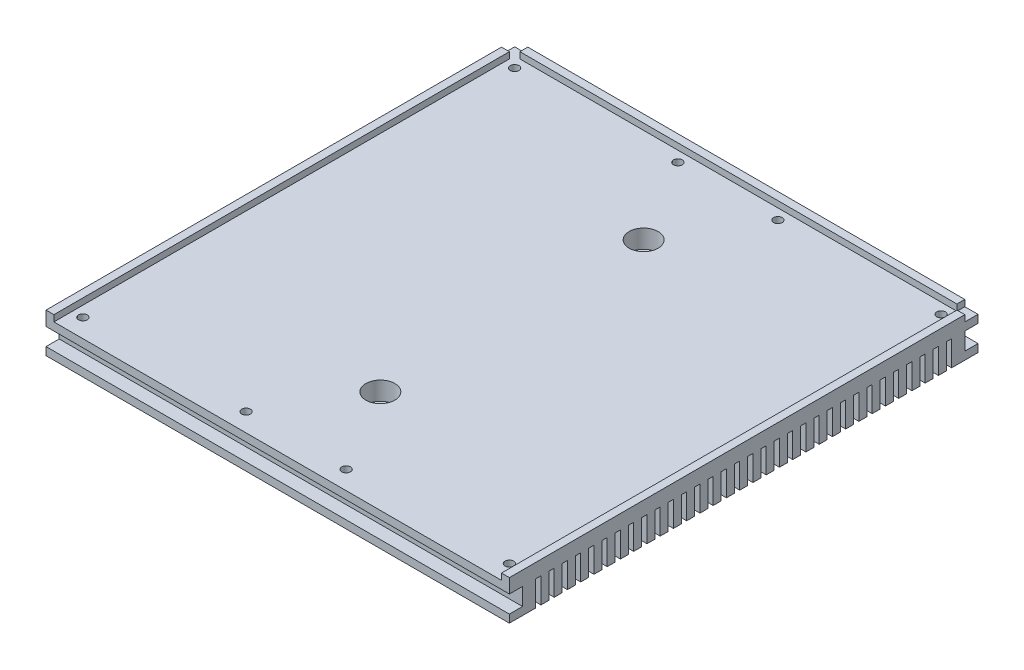
SolidWorks part; units mm, degrees
material "6061 合金"
ref_plane "前视基准面" through (0, 0, 0) normal (0, 0, 1) x (1, 0, 0)
ref_plane "上视基准面" through (0, 0, 0) normal (0, 1, 0) x (1, 0, 0)
ref_plane "右视基准面" through (0, 0, 0) normal (1, 0, 0) x (0, 0, -1)
sketch "草图1" plane through (0, 12.6, 0) normal (0, 1, 0) x (1, 0, 0)
  line L0 (-100.7481, -361.7245) -> (-100.7481, -517.7245) construction
  line L1 (72.2519, -528.7245) -> (-103.7481, -528.7245)
  line L2 (72.2519, -528.7245) -> (72.2519, -350.7245)
  line L3 (72.2519, -350.7245) -> (-103.7481, -350.7245)
  line L4 (-103.7481, -528.7245) -> (-103.7481, -350.7245)
  line L5 (7.2519, -525.7245) -> (61.2519, -525.7245) construction
  line L6 (69.2519, -517.7245) -> (69.2519, -361.7245) construction
  line L9 (61.2519, -353.7245) -> (7.2519, -353.7245) construction
  dimension "D1" = 3
  dimension "D2" = 3
  dimension "D3" = 3
  dimension "D4" = 3
extrude "凸台-拉伸1" add sketch "草图1" against normal up to surface (12.6 mm away)
sketch "草图3" plane through (0, 12.6, 0) normal (0, 1, 0) x (1, 0, 0)
  line L0 (-15.7481, -539.7245) -> (-15.7481, -489.7245) construction
  line L1 (-15.7481, -489.7245) -> (-15.7481, -389.7245) construction
  dimension "D1" = 50
  dimension "D2" = 100
hole_wizard "打孔尺寸(%根据)内六角圆柱头螺钉的类型1" positions "3D草图1" profile "草图4" counterbore size "M6" standard "GB" end condition through all
sketch3d "3D草图1"
  point P0 (-15.7481, 12.6, 389.7245)
  point P3 (-15.7481, 12.6, 489.7245)
sketch "草图4" plane through (-15.7481, 12.6, 389.7245) normal (1, 0, 0) x (0, 0, 1)
  line L0 (0, 0) -> (0, 12.6)
  line L1 (0, 12.6) -> (3.3, 12.6)
  line L3 (3.3, 12.6) -> (3.3, 7)
  line L4 (3.3, 7) -> (5.5, 7)
  line L5 (5.5, 7) -> (5.5, 0)
  line L7 (5.5, 0) -> (0, 0)
  line L11 (0, -6.35) -> (0, 107.95) construction
  dimension "通孔孔直径" = 6.6
  dimension "通孔孔深度" = 12.6
  dimension "柱形沉头孔直径" = 11
  dimension "柱形沉头孔深度" = 7
sketch "草图5" plane through (0, 0, 528.7245) normal (0, 0, 1) x (1, 0, 0)
  line L0 (72.2519, 0) -> (-103.7481, 0) construction
  line L1 (-98.7481, 0) -> (-96.7481, 0)
  line L2 (-98.7481, 0) -> (-98.7481, 7.6)
  line L3 (-98.7481, 7.6) -> (-96.7481, 7.6)
  line L4 (-96.7481, 0) -> (-96.7481, 7.6)
  line L5 (-103.7481, 0) -> (-103.7481, 12.6) construction
  line L6 (-103.7481, 12.6) -> (72.2519, 12.6) construction
  dimension "D1" = 5
  dimension "D2" = 5
  dimension "D3" = 2
extrude "切除-拉伸2" [suppressed] cut sketch "草图5" against normal through all
pattern_linear "阵列(线性)1" [suppressed] count 30 spacing 5.6552 of bodies 104
sketch "草图6" [suppressed] plane through (0, 0, 0) normal (0, -1, 0) x (1, 0, 0)
  line L0 (-8.2654, 528.7245) -> (-23.2309, 528.7245) construction
  line L1 (-19.5757, 528.7245) -> (-17.5757, 528.7245)
  line L2 (-19.5757, 528.7245) -> (-19.5757, 498.7245)
  line L3 (-19.5757, 498.7245) -> (-17.5757, 498.7245)
  line L4 (-17.5757, 528.7245) -> (-17.5757, 498.7245)
  line L5 (-25.2309, 528.7245) -> (-23.2309, 528.7245) construction
  line L6 (-25.2309, 528.7245) -> (-28.8861, 528.7245) construction
  line L7 (-19.5757, 528.7245) -> (-23.2309, 528.7245) construction
  line L8 (-17.5757, 528.7245) -> (-13.9205, 528.7245) construction
  line L9 (-13.9205, 528.7245) -> (-11.9205, 528.7245)
  line L10 (-13.9205, 528.7245) -> (-13.9205, 498.7245)
  line L11 (-13.9205, 498.7245) -> (-11.9205, 498.7245)
  line L12 (-11.9205, 528.7245) -> (-11.9205, 498.7245)
  line L13 (-23.2309, 350.7245) -> (-8.2654, 350.7245) construction
  line L14 (-19.5757, 350.7245) -> (-17.5757, 350.7245)
  line L15 (-19.5757, 350.7245) -> (-19.5757, 380.7245)
  line L16 (-19.5757, 380.7245) -> (-17.5757, 380.7245)
  line L17 (-17.5757, 350.7245) -> (-17.5757, 380.7245)
  line L19 (-13.9205, 350.7245) -> (-11.9205, 350.7245)
  line L20 (-13.9205, 350.7245) -> (-13.9205, 380.7245)
  line L21 (-13.9205, 380.7245) -> (-11.9205, 380.7245)
  line L22 (-11.9205, 350.7245) -> (-11.9205, 380.7245)
  dimension "D1" = 30
  dimension "D2" = 30
extrude "切除-拉伸3" [suppressed] cut sketch "草图6" against normal up to surface (7.6 mm away)
sketch "草图7" plane through (0, 12.6, 0) normal (0, 1, 0) x (1, 0, 0)
  line L0 (69.2519, -528.7245) -> (69.2519, -353.7245)
  line L1 (69.2519, -353.7245) -> (-100.7481, -353.7245)
  line L2 (-100.7481, -353.7245) -> (-100.7481, -528.7245)
  line L3 (69.2519, -528.7245) -> (72.2519, -528.7245)
  line L4 (72.2519, -528.7245) -> (72.2519, -350.7245)
  line L5 (72.2519, -350.7245) -> (-103.7481, -350.7245)
  line L6 (-103.7481, -350.7245) -> (-103.7481, -528.7245)
  line L7 (-103.7481, -528.7245) -> (72.2519, -528.7245)
  line L8 (72.2519, -528.7245) -> (72.2519, -350.7245)
  line L9 (72.2519, -350.7245) -> (-103.7481, -350.7245)
  line L10 (-103.7481, -350.7245) -> (-103.7481, -528.7245)
  line L11 (-103.7481, -528.7245) -> (-100.7481, -528.7245)
  dimension "D1" = 0
  dimension "D2" = 3
extrude "凸台-拉伸3" add sketch "草图7" along normal offset from surface (2.4 mm away) 15 up to face at (-15.7481, 0, 393.0245)
sketch "草图8" plane through (0, 15, 0) normal (0, 1, 0) x (1, 0, 0)
  line L1 (-103.7481, -350.7245) -> (-98.7481, -350.7245)
  line L2 (-103.7481, -350.7245) -> (-103.7481, -355.7245)
  line L3 (-103.7481, -355.7245) -> (-98.7481, -355.7245)
  line L4 (-98.7481, -350.7245) -> (-98.7481, -355.7245)
  line L5 (72.2519, -350.7245) -> (67.2519, -350.7245)
  line L6 (72.2519, -350.7245) -> (72.2519, -355.7245)
  line L7 (72.2519, -355.7245) -> (67.2519, -355.7245)
  line L8 (67.2519, -350.7245) -> (67.2519, -355.7245)
  dimension "D1" = 5
  dimension "D2" = 5
  dimension "D3" = 5
  dimension "D4" = 5
extrude "切除-拉伸4" cut sketch "草图8" against normal up to surface (2.4 mm away) up to face at (-15.7481, 12.6, 441.2245)
sketch "草图9" plane through (0, 12.6, 0) normal (0, 1, 0) x (1, 0, 0)
  line L1 (-96.7481, -357.7245) -> (-34.7481, -357.7245)
  line L2 (-96.7481, -357.7245) -> (-96.7481, -521.7245)
  line L3 (-96.7481, -521.7245) -> (-34.7481, -521.7245)
  line L4 (-34.7481, -357.7245) -> (-34.7481, -521.7245)
  line L5 (3.2519, -521.7245) -> (65.2519, -521.7245)
  line L6 (3.2519, -521.7245) -> (3.2519, -357.7245)
  line L7 (3.2519, -357.7245) -> (65.2519, -357.7245)
  line L8 (65.2519, -521.7245) -> (65.2519, -357.7245)
hole_wizard "M4 螺纹孔1" positions "3D草图2" profile "草图10" tap size "M4" standard "GB"
sketch3d "3D草图2"
  point P0 (-96.7481, 12.6, 357.7245)
  point P3 (-34.7481, 12.6, 357.7245)
  point P6 (-34.7481, 12.6, 521.7245)
  point P9 (-96.7481, 12.6, 521.7245)
  point P12 (3.2519, 12.6, 521.7245)
  point P15 (65.2519, 12.6, 521.7245)
  point P18 (65.2519, 12.6, 357.7245)
  point P21 (3.2519, 12.6, 357.7245)
sketch "草图10" plane through (-96.7481, 12.6, 357.7245) normal (1, 0, 0) x (0, 0, 1)
  line L0 (0, 0) -> (0, 5.9914)
  line L1 (0, 5.9914) -> (1.65, 5)
  line L2 (1.65, 5) -> (1.65, 0)
  line L5 (1.65, 0) -> (0, 0)
  line L10 (0, 5.9914) -> (-1.65, 5) construction
  line L11 (0, -6.35) -> (0, 107.95) construction
  dimension "螺纹孔钻头直径" = 3.3
  dimension "螺纹孔钻头深度" = 5
  dimension "导头角度" = 118
cosmetic thread "孔螺蚊线1" parameters "D1"=5, "D2"=4
cosmetic thread "孔螺蚊线2" parameters "D1"=5, "D2"=4
cosmetic thread "孔螺蚊线3" parameters "D1"=5, "D2"=4
cosmetic thread "孔螺蚊线4" parameters "D1"=5, "D2"=4
cosmetic thread "孔螺蚊线5" parameters "D1"=5, "D2"=4
cosmetic thread "孔螺蚊线6" parameters "D1"=5, "D2"=4
cosmetic thread "孔螺蚊线7" parameters "D1"=5, "D2"=4
cosmetic thread "孔螺蚊线8" parameters "D1"=5, "D2"=4
sketch "草图11" plane through (0, 0, 0) normal (0, -1, 0) x (1, 0, 0)
  line L0 (-15.7481, 489.7245) -> (-15.7481, 479.7245) construction
  line L1 (-15.7481, 489.7245) -> (-15.7481, 389.7245) construction
  line L2 (-15.7481, 389.7245) -> (-15.7481, 399.7245) construction
  dimension "D1" = 10
  dimension "D2" = 10
hole_wizard "大小mm 暗销孔1" positions "3D草图3" profile "草图12" hole size "Ø4.0" standard "GB"
sketch3d "3D草图3"
  point P0 (-15.7481, 0, 479.7245)
sketch "草图12" plane through (-15.7481, 0, 479.7245) normal (1, 0, 0) x (0, 0, -1)
  line L0 (0, 0) -> (0, 6.2017)
  line L1 (0, 6.2017) -> (2, 5)
  line L2 (2, 5) -> (2, 0)
  line L5 (2, 0) -> (0, 0)
  line L10 (0, 6.2017) -> (-2, 5) construction
  line L11 (0, -6.35) -> (0, 107.95) construction
  dimension "孔直径" = 4
  dimension "孔深度" = 5
  dimension "导头角度" = 118
sketch "草图13" plane through (0, 0, 0) normal (0, -1, 0) x (1, 0, 0)
  line L0 (-15.7481, 398.7245) -> (-15.7481, 400.7245) construction
  line L1 (-15.7481, 489.7245) -> (-15.7481, 389.7245) construction
  line L2 (-17.7481, 398.7245) -> (-17.7481, 400.7245)
  line L3 (-13.7481, 398.7245) -> (-13.7481, 400.7245)
  arc A0 (-17.7481, 398.7245) -> (-13.7481, 398.7245) centre (-15.7481, 398.7245) ccw
  arc A1 (-13.7481, 400.7245) -> (-17.7481, 400.7245) centre (-15.7481, 400.7245) ccw
  point P5 (-15.7481, 399.7245)
  dimension "D1" = 2
  dimension "D2" = 2
extrude "切除-拉伸5" cut sketch "草图13" against normal blind 5
sketch "草图14" plane through (-103.7481, 0, 0) normal (-1, 0, 0) x (0, 0, 1)
  line L0 (355.7245, 12.6) -> (350.7245, 12.6) construction
  line L1 (528.7245, 3) -> (523.7245, 3)
  line L2 (528.7245, 3) -> (528.7245, 9.6)
  line L3 (528.7245, 9.6) -> (523.7245, 9.6)
  line L4 (523.7245, 3) -> (523.7245, 9.6)
  line L5 (350.7245, 3) -> (355.7245, 3)
  line L6 (350.7245, 3) -> (350.7245, 9.6)
  line L7 (350.7245, 9.6) -> (355.7245, 9.6)
  line L8 (355.7245, 3) -> (355.7245, 9.6)
  line L9 (528.7245, 0) -> (350.7245, 0) construction
  line L10 (528.7245, 0) -> (528.7245, 15) construction
  dimension "D1" = 3
  dimension "D2" = 3
  dimension "D3" = 5
extrude "切除-拉伸6" cut sketch "草图14" against normal through all
sketch "草图15" plane through (-103.7481, 0, 0) normal (-1, 0, 0) x (0, 0, 1)
  line L0 (528.7245, 0) -> (350.7245, 0) construction
  line L1 (518.7245, 0) -> (516.7245, 0)
  line L2 (518.7245, 0) -> (518.7245, 9.6)
  line L3 (518.7245, 9.6) -> (516.7245, 9.6)
  line L4 (516.7245, 0) -> (516.7245, 9.6)
  line L5 (523.7245, 9.6) -> (523.7245, 3) construction
  line L6 (528.7245, 9.6) -> (523.7245, 9.6) construction
  dimension "D1" = 2
  dimension "D2" = 5
extrude "切除-拉伸7" cut sketch "草图15" against normal through all
pattern_linear "阵列(线性)3" count 32 spacing 5.0323 along (0, 0, -1) skipping (5, 0), (6, 0), (7, 0), (8, 0), (23, 0), (24, 0), (25, 0), (26, 0) of "切除-拉伸7"
sketch "草图16" plane through (0, 0, 0) normal (0, -1, 0) x (1, 0, 0)
  line L0 (-103.7481, 496.5955) -> (-103.7481, 473.4342) construction
  line L1 (-103.7481, 493.5632) -> (-23.2481, 493.5632)
  line L2 (-103.7481, 493.5632) -> (-103.7481, 491.5632)
  line L3 (-103.7481, 491.5632) -> (-23.2481, 491.5632)
  line L4 (-23.2481, 493.5632) -> (-23.2481, 491.5632)
  line L5 (72.2519, 473.4342) -> (72.2519, 496.5955) construction
  line L6 (72.2519, 493.5632) -> (-8.2481, 493.5632)
  line L7 (72.2519, 493.5632) -> (72.2519, 491.5632)
  line L8 (72.2519, 491.5632) -> (-8.2481, 491.5632)
  line L9 (-8.2481, 493.5632) -> (-8.2481, 491.5632)
  line L10 (-15.7481, 539.7245) -> (-15.7481, 489.7245) construction
  line L11 (-15.7481, 489.7245) -> (-15.7481, 389.7245) construction
  line L12 (-103.7481, 498.5955) -> (-103.7481, 496.5955) construction
  line L13 (-103.7481, 493.5632) -> (-103.7481, 496.5955) construction
  line L14 (-103.7481, 501.6277) -> (-103.7481, 498.5955) construction
  dimension "D1" = 7.5
  dimension "D2" = 7.5
extrude "切除-拉伸8" cut sketch "草图16" against normal up to surface (9.6 mm away) up to face at (-15.7481, 9.6, 497.5955)
pattern_linear "阵列(线性)4" count 27 spacing 5.0323 along (0, 0, -1) of "切除-拉伸8"
